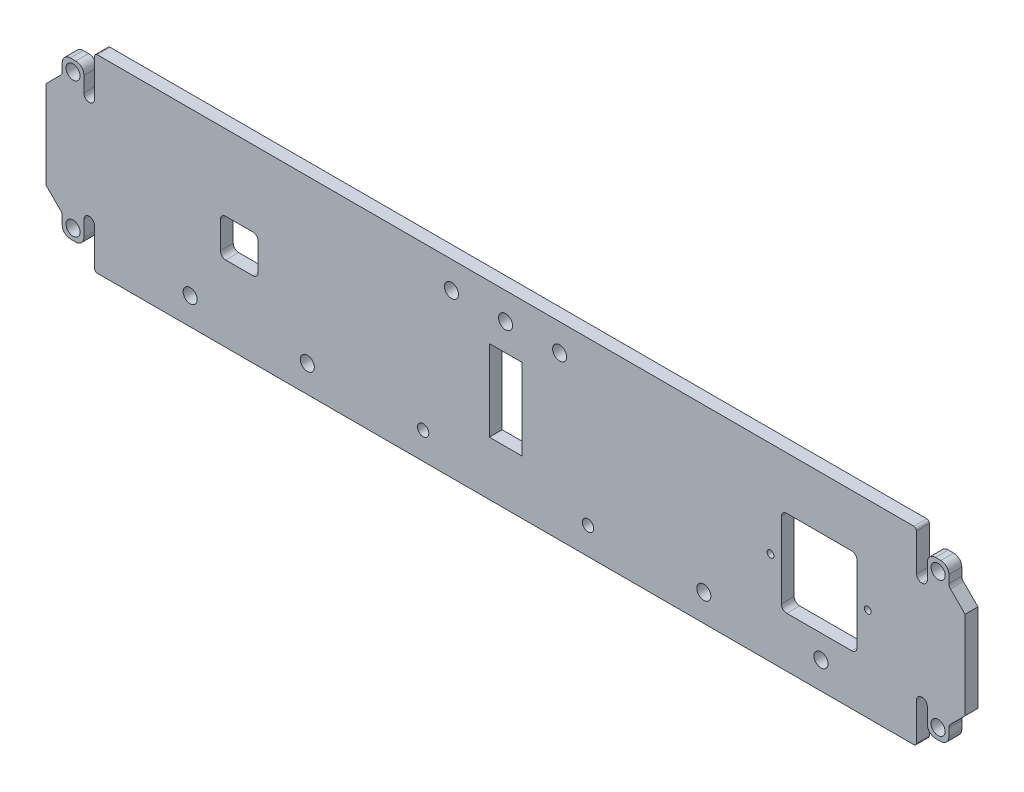
SolidWorks part; units mm, degrees
ref_plane "Front Plane" through (0, 0, 0) normal (0, 0, 1) x (1, 0, 0)
ref_plane "Top Plane" through (0, 0, 0) normal (0, 1, 0) x (1, 0, 0)
ref_plane "Right Plane" through (0, 0, 0) normal (1, 0, 0) x (0, 0, -1)
ref_plane "Plane1" through (0, 0, 0) normal (0, 0, -1) x (-1, 0, 0)
sketch "Sketch11" plane through (0, 0, 0) normal (0, 0, -1) x (-1, 0, 0)
  line L0 (-17.9762, 1) -> (-17.9762, 14.7547)
  line L1 (-14.0074, 14.7547) -> (-14.0074, 9)
  line L2 (-11.0074, 6) -> (-9, 6)
  line L3 (-6, 9) -> (-6, 11.9171)
  line L4 (-5.4188, 13.3202) -> (0, 18.739)
  line L5 (0, 18.739) -> (0, 51.261)
  line L6 (0, 51.261) -> (-5.4188, 56.6798)
  line L7 (-6, 58.0829) -> (-6, 61)
  line L8 (-9, 64) -> (-11.0074, 64)
  line L9 (-14.0074, 61) -> (-14.0074, 55.2453)
  line L10 (-17.9762, 55.2453) -> (-17.9762, 69)
  line L11 (-18.9762, 70) -> (-321.0238, 70)
  line L12 (-322.0238, 69) -> (-322.0238, 55.2453)
  line L13 (-324.0082, 53.261) -> (-324.0395, 53.261)
  line L14 (-326.0238, 55.2453) -> (-326.0238, 61)
  line L15 (-329.0238, 64) -> (-331, 64)
  line L16 (-334, 61) -> (-334, 58.0829)
  line L17 (-334.5812, 56.6798) -> (-340, 51.261)
  line L18 (-340, 51.261) -> (-340, 18.739)
  line L19 (-340, 18.739) -> (-334.5812, 13.3202)
  line L20 (-334, 11.9171) -> (-334, 9)
  line L21 (-331, 6) -> (-329.0238, 6)
  line L22 (-326.0238, 9) -> (-326.0238, 14.7547)
  line L23 (-324.0395, 16.739) -> (-324.0082, 16.739)
  line L24 (-322.0238, 14.7547) -> (-322.0238, 1)
  line L25 (-321.0238, 0) -> (-18.9762, 0)
  arc A0 (-17.9762, 14.7547) -> (-14.0074, 14.7547) centre (-15.9918, 14.7547) cw
  arc A1 (-14.0074, 9) -> (-11.0074, 6) centre (-11.0074, 9) ccw
  arc A2 (-9, 6) -> (-6, 9) centre (-9, 9) ccw
  arc A3 (-6, 11.9171) -> (-5.4188, 13.3202) centre (-4.0156, 11.9171) cw
  arc A4 (-5.4188, 56.6798) -> (-6, 58.0829) centre (-4.0156, 58.0829) cw
  arc A5 (-6, 61) -> (-9, 64) centre (-9, 61) ccw
  arc A6 (-11.0074, 64) -> (-14.0074, 61) centre (-11.0074, 61) ccw
  arc A7 (-14.0074, 55.2453) -> (-17.9762, 55.2453) centre (-15.9918, 55.2453) cw
  arc A8 (-17.9762, 69) -> (-18.9762, 70) centre (-18.9762, 69) ccw
  arc A9 (-321.0238, 70) -> (-322.0238, 69) centre (-321.0238, 69) ccw
  arc A10 (-322.0238, 55.2453) -> (-324.0082, 53.261) centre (-324.0082, 55.2453) cw
  arc A11 (-324.0395, 53.261) -> (-326.0238, 55.2453) centre (-324.0395, 55.2453) cw
  arc A12 (-326.0238, 61) -> (-329.0238, 64) centre (-329.0238, 61) ccw
  arc A13 (-331, 64) -> (-334, 61) centre (-331, 61) ccw
  arc A14 (-334, 58.0829) -> (-334.5812, 56.6798) centre (-335.9844, 58.0829) cw
  arc A15 (-334.5812, 13.3202) -> (-334, 11.9171) centre (-335.9844, 11.9171) cw
  arc A16 (-334, 9) -> (-331, 6) centre (-331, 9) ccw
  arc A17 (-329.0238, 6) -> (-326.0238, 9) centre (-329.0238, 9) ccw
  arc A18 (-326.0238, 14.7547) -> (-324.0395, 16.739) centre (-324.0395, 14.7547) cw
  arc A19 (-324.0082, 16.739) -> (-322.0238, 14.7547) centre (-324.0082, 14.7547) cw
  arc A20 (-322.0238, 1) -> (-321.0238, 0) centre (-321.0238, 1) ccw
  arc A21 (-18.9762, 0) -> (-17.9762, 1) centre (-18.9762, 1) ccw
base flange "Base-Flange1" sketch "Sketch11" thickness 4.7625 reverse thickness direction yes parameters "D1"=0
sketch "Sketch16" plane through (0, 0, 0) normal (0, 0, -1) x (-1, 0, 0)
  line L0 (-274, 50.5977) -> (-298, 50.5977)
  line L1 (-300, 48.5977) -> (-300, 20.5977)
  line L2 (-298, 18.5977) -> (-274, 18.5977)
  line L3 (-272, 20.5977) -> (-272, 48.5977)
  arc A0 (-272, 48.5977) -> (-274, 50.5977) centre (-274, 48.5977) ccw
  arc A1 (-298, 50.5977) -> (-300, 48.5977) centre (-298, 48.5977) ccw
  arc A2 (-300, 20.5977) -> (-298, 18.5977) centre (-298, 20.5977) ccw
  arc A3 (-274, 18.5977) -> (-272, 20.5977) centre (-274, 20.5977) ccw
extrude "Cut-Extrude1" cut sketch "Sketch16" against normal through all
sketch "Sketch17" plane through (0, 0, 0) normal (0, 0, -1) x (-1, 0, 0)
  line L0 (-64.5, 30) -> (-64.5, 40)
  line L1 (-66.5, 42) -> (-76.5, 42)
  line L2 (-78.5, 40) -> (-78.5, 30)
  line L3 (-76.5, 28) -> (-66.5, 28)
  line L4 (0, 18.739) -> (0, 51.261) construction
  line L5 (-321.0238, 0) -> (-18.9762, 0) construction
  arc A0 (-64.5, 40) -> (-66.5, 42) centre (-66.5, 40) ccw
  arc A1 (-76.5, 42) -> (-78.5, 40) centre (-76.5, 40) ccw
  arc A2 (-78.5, 30) -> (-76.5, 28) centre (-76.5, 30) ccw
  arc A3 (-66.5, 28) -> (-64.5, 30) centre (-66.5, 30) ccw
  dimension "D5" = 2
  dimension "D6" = 2
  dimension "D7" = 2
  dimension "D8" = 2
  dimension "D1" = 14
  dimension "D2" = 64.5
  dimension "D3" = 28
  dimension "D4" = 14
extrude "Cut-Extrude2" cut sketch "Sketch17" against normal through all
sketch "Sketch18" plane through (0, 0, 0) normal (0, 0, -1) x (-1, 0, 0)
  line L0 (-41.024, 36.6) -> (-47.824, 36.6)
  line L1 (-47.824, 33.4) -> (-41.024, 33.4)
  arc A0 (-47.824, 36.6) -> (-47.824, 33.4) centre (-47.824, 35) ccw
  arc A1 (-41.024, 33.4) -> (-41.024, 36.6) centre (-41.024, 35) ccw
extrude "Cut-Extrude3" [suppressed] cut sketch "Sketch18" against normal through all
sketch "Sketch19" plane through (0, 0, 0) normal (0, 0, -1) x (-1, 0, 0)
  line L0 (-70.424, 36.6) -> (-77.224, 36.6)
  line L1 (-77.224, 33.4) -> (-70.424, 33.4)
  arc A0 (-77.224, 36.6) -> (-77.224, 33.4) centre (-77.224, 35) ccw
  arc A1 (-70.424, 33.4) -> (-70.424, 36.6) centre (-70.424, 35) ccw
extrude "Cut-Extrude4" [suppressed] cut sketch "Sketch19" against normal through all
sketch "Sketch20" plane through (0, 0, 4.7625) normal (0, 0, 1) x (1, 0, 0)
  line L0 (176, 20) -> (176, 50)
  line L1 (176, 50) -> (164, 50)
  line L2 (164, 50) -> (164, 20)
  line L3 (164, 20) -> (176, 20)
extrude "Cut-Extrude5" cut sketch "Sketch20" against normal through all
hole_wizard "Ø5.2 (5.2) Diameter Hole1" positions "Sketch22" profile "Sketch21" hole size "Ø5.2" standard "ANSI Metric"
sketch "Sketch22" plane through (0, 0, 4.7625) normal (0, 0, 1) x (1, 0, 0)
  point P0 (170, 60)
  point P1 (330, 60)
  point P2 (10, 10)
  point P3 (10, 60)
  point P4 (330, 10)
  point P5 (150, 60)
  point P6 (190, 60)
  point P7 (53.3333, 10)
  point P8 (96.6667, 10)
  point P9 (243.3333, 10)
  point P10 (286.6667, 10)
sketch "Sketch21" plane through (170, 60, 4.7625) normal (1, 0, 0) x (0, -1, 0)
  line L0 (0, 0) -> (0, 4.7625)
  line L1 (0, 4.7625) -> (2.6, 4.7625)
  line L2 (2.6, 4.7625) -> (2.6, 0)
  line L5 (2.6, 0) -> (0, 0)
  line L11 (0, -6.35) -> (0, 107.95) construction
  dimension "Thru Hole Dia." = 5.2
  dimension "Thru Hole Depth" = 4.7625
hole_wizard "Ø4.2 (4.2) Diameter Hole1" positions "Sketch24" profile "Sketch23" hole size "Ø4.2" standard "ANSI Metric"
sketch "Sketch24" plane through (0, 0, 0) normal (0, 0, -1) x (-1, 0, 0)
  point P0 (-200.5, 10)
  point P1 (-139.5, 10)
sketch "Sketch23" plane through (200.5, 10, 0) normal (1, 0, 0) x (0, 1, 0)
  line L0 (0, 0) -> (0, 4.7625)
  line L1 (0, 4.7625) -> (2.1, 4.7625)
  line L2 (2.1, 4.7625) -> (2.1, 0)
  line L5 (2.1, 0) -> (0, 0)
  line L11 (0, -6.35) -> (0, 107.95) construction
  dimension "Thru Hole Dia." = 4.2
  dimension "Thru Hole Depth" = 4.7625
hole_wizard "Ø2.5 (2.5) Diameter Hole1" positions "Sketch26" profile "Sketch25" hole size "Ø2.5" standard "ANSI Metric"
sketch "Sketch26" plane through (0, 0, 0) normal (0, 0, -1) x (-1, 0, 0)
  point P0 (-304, 34.5977)
  point P1 (-268, 34.5977)
sketch "Sketch25" plane through (304, 34.5977, 0) normal (1, 0, 0) x (0, 1, 0)
  line L0 (0, 0) -> (0, 4.7625)
  line L1 (0, 4.7625) -> (1.25, 4.7625)
  line L2 (1.25, 4.7625) -> (1.25, 0)
  line L5 (1.25, 0) -> (0, 0)
  line L11 (0, -6.35) -> (0, 107.95) construction
  dimension "Thru Hole Dia." = 2.5
  dimension "Thru Hole Depth" = 4.7625
sketch "Bend-Lines4" plane through (0, 0, 0) normal (0, 1, 0) x (1, 0, 0)
sketch "Bounding-Box4" plane through (0, 0, 0) normal (0, 1, 0) x (1, 0, 0)
sheet metal parameters "Sheet-Metal(5)" thickness 4.7625 parameters "D1"=0
flat pattern "Flat-Pattern(5)" [suppressed]
sketch "Bend-Lines5" plane through (0, 0, 0) normal (0, 1, 0) x (1, 0, 0)
sketch "Bounding-Box5" [suppressed] plane through (0, 0, 0) normal (0, 1, 0) x (1, 0, 0)
sheet metal parameters "Sheet-Metal(6)" thickness 4.7625 parameters "D1"=0
flat pattern "Flat-Pattern(5)"
sketch "Bend-Lines5" plane through (0, 0, 0) normal (0, 1, 0) x (1, 0, 0)
sketch "Bounding-Box5" [suppressed] plane through (0, 0, 0) normal (0, 1, 0) x (1, 0, 0)
sheet metal parameters "Sheet-Metal(7)" thickness 4.7625 parameters "D1"=0
flat pattern "Flat-Pattern(5)"
sketch "Bend-Lines5" plane through (0, 0, 0) normal (0, 1, 0) x (1, 0, 0)
sketch "Bounding-Box5" [suppressed] plane through (0, 0, 0) normal (0, 1, 0) x (1, 0, 0)
sheet metal parameters "Sheet-Metal(8)" thickness 4.7625 parameters "D1"=0
flat pattern "Flat-Pattern(5)"
sketch "Bend-Lines5" plane through (0, 0, 0) normal (0, 1, 0) x (1, 0, 0)
sketch "Bounding-Box5" [suppressed] plane through (0, 0, 0) normal (0, 1, 0) x (1, 0, 0)
sheet metal parameters "Sheet-Metal(9)" thickness 4.7625 parameters "D1"=0
flat pattern "Flat-Pattern(5)"
sketch "Bend-Lines5" plane through (0, 0, 0) normal (0, 1, 0) x (1, 0, 0)
sketch "Bounding-Box5" [suppressed] plane through (0, 0, 0) normal (0, 1, 0) x (1, 0, 0)
sheet metal parameters "Sheet-Metal(10)" thickness 4.7625 parameters "D1"=0
flat pattern "Flat-Pattern(5)"
sketch "Bend-Lines5" plane through (0, 0, 0) normal (0, 1, 0) x (1, 0, 0)
sketch "Bounding-Box5" [suppressed] plane through (0, 0, 0) normal (0, 1, 0) x (1, 0, 0)
sheet metal parameters "Sheet-Metal(11)" thickness 4.7625 parameters "D1"=0
flat pattern "Flat-Pattern(5)"
sketch "Bend-Lines5" plane through (0, 0, 0) normal (0, 1, 0) x (1, 0, 0)
sketch "Bounding-Box5" [suppressed] plane through (0, 0, 0) normal (0, 1, 0) x (1, 0, 0)
sheet metal parameters "Sheet-Metal(12)" thickness 4.7625 parameters "D1"=0
flat pattern "Flat-Pattern(5)"
sketch "Bend-Lines5" plane through (0, 0, 0) normal (0, 1, 0) x (1, 0, 0)
sketch "Bounding-Box5" [suppressed] plane through (0, 0, 0) normal (0, 1, 0) x (1, 0, 0)
sheet metal parameters "Sheet-Metal(13)" thickness 4.7625 parameters "D1"=0
flat pattern "Flat-Pattern(5)"
sketch "Bend-Lines5" plane through (0, 0, 0) normal (0, 1, 0) x (1, 0, 0)
sketch "Bounding-Box5" [suppressed] plane through (0, 0, 0) normal (0, 1, 0) x (1, 0, 0)
